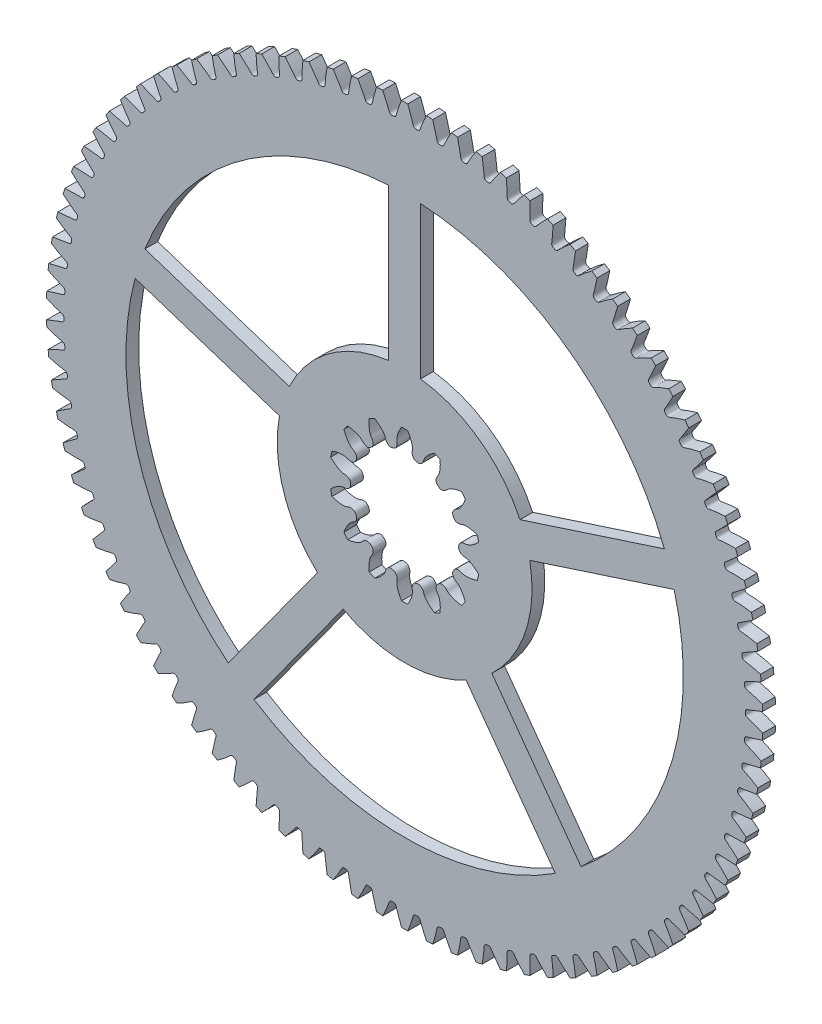
SolidWorks part; units mm, degrees
ref_plane "Alzado" through (0, 0, 0) normal (0, 0, 1) x (1, 0, 0)
ref_plane "Planta" through (0, 0, 0) normal (0, 1, 0) x (1, 0, 0)
ref_plane "Vista lateral" through (0, 0, 0) normal (1, 0, 0) x (0, 0, -1)
ref_axis "Eje1" through (0, 0, 55) along (0, 0, -1)
sketch "SketchRevolveEngranaje Fijo(11.2)" plane through (0, 0, 0) normal (1, 0, 0) x (0, 0, -1)
  line L0 (0, 0) -> (1, 0) construction
  line L1 (-0.1, 0) -> (-0.1, 5.6222)
  line L2 (-0.1, 5.6222) -> (0.1, 5.6222)
  line L3 (0.1, 5.6222) -> (0.1, 0)
  line L4 (0.1, 0) -> (-0.1, 0)
revolve "Engranaje Fijo(11.2)" add sketch "SketchRevolveEngranaje Fijo(11.2)" angle 360 about L0
sketch "SketchToothEngranaje Fijo(11.2)" plane through (0, 0, 0) normal (0, 0, 1) x (1, 0, 0)
  arc A0 (5.6263, 0.1499) -> (5.6263, -0.1499) centre (0, 0) cw
  spline S0 degree 3 poles (5.6263, -0.1499) (5.6166, -0.1454) (5.6021, -0.1388) (5.5829, -0.1304) (5.5688, -0.1243) (5.5549, -0.1184) (5.5413, -0.1127) (5.5278, -0.1072) (5.5146, -0.102) (5.5016, -0.0969) (5.4888, -0.092) (5.4762, -0.0873) (5.4639, -0.0828) (5.4518, -0.0785) (5.4399, -0.0744) (5.4282, -0.0704) (5.4168, -0.0666) (5.4057, -0.063) (5.3936, -0.0592) (5.3845, -0.0566) (5.3783, -0.0544) (5.3759, -0.0535) (5.3735, -0.0525) (5.371, -0.0513) (5.3684, -0.0498) (5.3656, -0.0481) (5.3626, -0.0459) (5.3594, -0.0431) (5.3561, -0.0395) (5.3528, -0.0348) (5.3498, -0.0288) (5.3477, -0.0218) (5.3469, -0.012) (5.3474, 0) (5.3469, 0.012) (5.3477, 0.0218) (5.3498, 0.0288) (5.3528, 0.0348) (5.3561, 0.0395) (5.3594, 0.0431) (5.3626, 0.0459) (5.3656, 0.0481) (5.3684, 0.0498) (5.371, 0.0513) (5.3735, 0.0525) (5.3759, 0.0535) (5.3783, 0.0544) (5.3845, 0.0566) (5.3936, 0.0592) (5.4057, 0.063) (5.4168, 0.0666) (5.4282, 0.0704) (5.4399, 0.0744) (5.4518, 0.0785) (5.4639, 0.0828) (5.4762, 0.0873) (5.4888, 0.092) (5.5016, 0.0969) (5.5146, 0.102) (5.5278, 0.1072) (5.5413, 0.1127) (5.5549, 0.1184) (5.5688, 0.1243) (5.5829, 0.1304) (5.6021, 0.1388) (5.6166, 0.1454) (5.6263, 0.1499) knots 0 0 0 0 0.047965 0.071326 0.094273 0.116806 0.138924 0.160627 0.181917 0.202792 0.223252 0.243298 0.26293 0.282148 0.300951 0.31934 0.337314 0.354874 0.37202 0.393934 0.397608 0.401368 0.40527 0.409387 0.413812 0.418671 0.424124 0.430371 0.437648 0.446186 0.45612 0.467339 0.478619 0.5 0.521381 0.532661 0.54388 0.553814 0.562352 0.569629 0.575876 0.581329 0.586188 0.590613 0.59473 0.598632 0.602392 0.606066 0.62798 0.645126 0.662686 0.68066 0.699049 0.717852 0.73707 0.756702 0.776748 0.797208 0.818083 0.839373 0.861076 0.883194 0.905727 0.928674 0.952035 1 1 1 1
extrude "ToothExtrudeCutEngranaje Fijo(11.2)" cut sketch "SketchToothEngranaje Fijo(11.2)" against normal blind 0.1 and the other way blind 0.1
pattern_circular "PatternEngranaje Fijo(11.2)" count 90 every 4 about axis through (0, 0, 55) along (0, 0, -1) of "ToothExtrudeCutEngranaje Fijo(11.2)"
sketch "AuxiliarySketchEngranaje Fijo(11.2)" plane through (0, 0, 0) normal (0, 0, 1) x (1, 0, 0)
  circle A0 centre (0, 0) radius 5.5 construction
  circle A1 centre (0, 0) radius 5.1683 construction
  circle A2 centre (0, 0) radius 5.383 construction
  circle A3 centre (0, 0) radius 5.6222 construction
  circle A4 centre (0, 0) radius 5.3472 construction
  dimension "PitchDiameter" = 11
  dimension "BaseDiameter" = 10.3366
  dimension "FormDiameter" = 10.7659
  dimension "MajorDiameter" = 11.2444
  dimension "MinorDiameter" = 10.6944
sketch "Croquis5" plane through (0, 0, 0.1) normal (0, 0, 1) x (1, 0, 0)
  line L0 (0, 0) -> (0, 4.375) construction
  line L1 (0, 0) -> (-4.1609, 1.3519) construction
  line L2 (0, 0) -> (4.1609, 1.3519) construction
  line L3 (0, 0) -> (-2.5716, -3.5394) construction
  line L4 (0, 0) -> (2.5716, -3.5394) construction
  line L15 (0.25, 1.9843) -> (0.25, 4.375)
  line L16 (-0.25, 1.9843) -> (-0.25, 4.375)
  line L18 (-1.8099, 0.851) -> (-4.0836, 1.5897)
  line L20 (-1.9644, 0.3754) -> (-4.2381, 1.1142)
  line L22 (1.8099, 0.851) -> (4.0836, 1.5897)
  line L24 (1.9644, 0.3754) -> (4.2381, 1.1142)
  line L26 (1.3686, -1.4584) -> (2.7738, -3.3925)
  line L28 (0.9641, -1.7523) -> (2.3693, -3.6864)
  line L30 (-0.9641, -1.7523) -> (-2.3693, -3.6864)
  line L32 (-1.3686, -1.4584) -> (-2.7738, -3.3925)
  arc A0 (1.3686, -1.4584) -> (1.9644, 0.3754) centre (0, 0) ccw
  arc A1 (-4.2313, 1.112) -> (-2.5716, -3.5394) centre (0, 0) ccw
  arc A3 (-0.25, 1.9843) -> (-1.8099, 0.851) centre (0, 0) ccw
  arc A4 (1.8099, 0.851) -> (0.25, 1.9843) centre (0, 0) ccw
  arc A5 (1.8099, 0.851) -> (0.25, 1.9843) centre (0, 0) ccw
  arc A6 (-0.9641, -1.7523) -> (0.9641, -1.7523) centre (0, 0) ccw
  arc A7 (0, 4.375) -> (-4.0768, 1.5875) centre (0, 0) ccw
  arc A8 (4.1609, 1.3519) -> (0, 4.375) centre (0, 0) ccw
  arc A9 (2.5716, -3.5394) -> (4.1609, 1.3519) centre (0, 0) ccw
  arc A10 (-2.5716, -3.5394) -> (2.5716, -3.5394) centre (0, 0) ccw
  arc A11 (-1.9644, 0.3754) -> (-1.3686, -1.4584) centre (0, 0) ccw
  arc A12 (-0.9641, -1.7523) -> (0.9641, -1.7523) centre (0, 0) ccw
  arc A13 (1.1619, 0.2163) -> (1.1406, 0.3093) centre (0, 0) ccw
  arc A14 (0.953, 0.699) -> (0.8935, 0.7735) centre (0, 0) ccw
  arc A15 (0.5553, 1.0432) -> (0.4694, 1.0846) centre (0, 0) ccw
  arc A16 (0.0477, 1.1809) -> (-0.0477, 1.1809) centre (0, 0) ccw
  arc A17 (-0.4694, 1.0846) -> (-0.5553, 1.0432) centre (0, 0) ccw
  arc A18 (-0.8935, 0.7735) -> (-0.953, 0.699) centre (0, 0) ccw
  arc A19 (-1.1406, 0.3093) -> (-1.1619, 0.2163) centre (0, 0) ccw
  arc A20 (-1.1619, -0.2163) -> (-1.1406, -0.3093) centre (0, 0) ccw
  arc A21 (-0.953, -0.699) -> (-0.8935, -0.7735) centre (0, 0) ccw
  arc A22 (-0.5553, -1.0432) -> (-0.4694, -1.0846) centre (0, 0) ccw
  arc A23 (-0.0477, -1.1809) -> (0.0477, -1.1809) centre (0, 0) ccw
  arc A24 (0.4694, -1.0846) -> (0.5553, -1.0432) centre (0, 0) ccw
  arc A25 (0.8935, -0.7735) -> (0.953, -0.699) centre (0, 0) ccw
  arc A26 (1.1406, -0.3093) -> (1.1619, -0.2163) centre (0, 0) ccw
  spline S0 degree 3 poles (1.1619, 0.2163) (1.1532, 0.2075) (1.1392, 0.1941) (1.1195, 0.1771) (1.104, 0.1645) (1.089, 0.1533) (1.0747, 0.1432) (1.061, 0.1344) (1.048, 0.1266) (1.0358, 0.1199) (1.0245, 0.1142) (1.014, 0.1093) (1.0046, 0.1054) (0.9961, 0.1021) (0.9887, 0.0996) (0.9823, 0.0977) (0.9738, 0.0954) (0.9644, 0.0944) (0.9543, 0.0941) (0.9465, 0.0934) (0.9389, 0.0924) (0.9315, 0.0913) (0.9244, 0.0898) (0.9175, 0.0881) (0.9108, 0.0861) (0.9043, 0.0838) (0.8981, 0.0813) (0.892, 0.0784) (0.8862, 0.0751) (0.8806, 0.0714) (0.8752, 0.0673) (0.87, 0.0627) (0.8651, 0.0575) (0.8606, 0.0516) (0.8566, 0.0449) (0.8533, 0.0376) (0.8508, 0.0295) (0.8496, 0.0218) (0.8491, 0.0119) (0.8497, 0) (0.8491, -0.0119) (0.8496, -0.0218) (0.8508, -0.0295) (0.8533, -0.0376) (0.8566, -0.0449) (0.8606, -0.0516) (0.8651, -0.0575) (0.87, -0.0627) (0.8752, -0.0673) (0.8806, -0.0714) (0.8862, -0.0751) (0.892, -0.0784) (0.8981, -0.0813) (0.9043, -0.0838) (0.9108, -0.0861) (0.9175, -0.0881) (0.9244, -0.0898) (0.9315, -0.0913) (0.9389, -0.0924) (0.9465, -0.0934) (0.9543, -0.0941) (0.9644, -0.0944) (0.9738, -0.0954) (0.9823, -0.0977) (0.9887, -0.0996) (0.9961, -0.1021) (1.0046, -0.1054) (1.014, -0.1093) (1.0245, -0.1142) (1.0358, -0.1199) (1.048, -0.1266) (1.061, -0.1344) (1.0747, -0.1432) (1.089, -0.1533) (1.104, -0.1645) (1.1195, -0.1771) (1.1392, -0.1941) (1.1532, -0.2075) (1.1619, -0.2163) knots 0.010866 0.010866 0.010866 0.010866 0.0554 0.080914 0.104969 0.127567 0.148706 0.168388 0.186612 0.203378 0.218686 0.232536 0.244928 0.255863 0.265339 0.273357 0.279918 0.297272 0.307044 0.316542 0.325781 0.334777 0.343546 0.352112 0.360499 0.368737 0.376863 0.384917 0.39295 0.401018 0.409187 0.41753 0.426123 0.43504 0.444343 0.454063 0.464189 0.474651 0.482386 0.5 0.517614 0.525349 0.535811 0.545937 0.555657 0.56496 0.573877 0.58247 0.590813 0.598982 0.60705 0.615083 0.623137 0.631263 0.639501 0.647888 0.656454 0.665223 0.674219 0.683458 0.692956 0.702728 0.720082 0.726643 0.734661 0.744137 0.755072 0.767464 0.781314 0.796622 0.813388 0.831612 0.851294 0.872433 0.895031 0.919086 0.9446 0.989134 0.989134 0.989134 0.989134
  spline S1 degree 3 poles (1.1406, -0.3093) (1.129, -0.3134) (1.1106, -0.3194) (1.0855, -0.3262) (1.0661, -0.3308) (1.0477, -0.3344) (1.0304, -0.3372) (1.0142, -0.3393) (0.9991, -0.3406) (0.9852, -0.3414) (0.9726, -0.3416) (0.9611, -0.3415) (0.9508, -0.3409) (0.9418, -0.3402) (0.934, -0.3392) (0.9274, -0.3382) (0.9187, -0.3366) (0.9099, -0.3334) (0.9006, -0.3293) (0.8933, -0.3265) (0.886, -0.3241) (0.8788, -0.3219) (0.8718, -0.3202) (0.8648, -0.3187) (0.8579, -0.3176) (0.8511, -0.3168) (0.8444, -0.3165) (0.8377, -0.3164) (0.831, -0.3169) (0.8244, -0.3177) (0.8177, -0.3191) (0.811, -0.321) (0.8044, -0.3236) (0.7977, -0.327) (0.7913, -0.3312) (0.7851, -0.3364) (0.7794, -0.3425) (0.7749, -0.349) (0.7702, -0.3577) (0.7655, -0.3687) (0.7599, -0.3791) (0.756, -0.3882) (0.7537, -0.3958) (0.7525, -0.4041) (0.7523, -0.4121) (0.753, -0.4198) (0.7545, -0.4271) (0.7566, -0.434) (0.7593, -0.4404) (0.7624, -0.4464) (0.7659, -0.4522) (0.7697, -0.4576) (0.7739, -0.4629) (0.7784, -0.4679) (0.7832, -0.4727) (0.7884, -0.4774) (0.7939, -0.482) (0.7997, -0.4864) (0.8058, -0.4906) (0.8122, -0.4948) (0.819, -0.4988) (0.828, -0.5035) (0.836, -0.5084) (0.8426, -0.5142) (0.8475, -0.5187) (0.8531, -0.5242) (0.8594, -0.5308) (0.8662, -0.5385) (0.8735, -0.5474) (0.8812, -0.5574) (0.8893, -0.5688) (0.8976, -0.5814) (0.9061, -0.5953) (0.9147, -0.6106) (0.9233, -0.6273) (0.9318, -0.6453) (0.9421, -0.6692) (0.949, -0.6873) (0.953, -0.699) knots 0.010866 0.010866 0.010866 0.010866 0.0554 0.080914 0.104969 0.127567 0.148706 0.168388 0.186612 0.203378 0.218686 0.232536 0.244928 0.255863 0.265339 0.273357 0.279918 0.297272 0.307044 0.316542 0.325781 0.334777 0.343546 0.352112 0.360499 0.368737 0.376863 0.384917 0.39295 0.401018 0.409187 0.41753 0.426123 0.43504 0.444343 0.454063 0.464189 0.474651 0.482386 0.5 0.517614 0.525349 0.535811 0.545937 0.555657 0.56496 0.573877 0.58247 0.590813 0.598982 0.60705 0.615083 0.623137 0.631263 0.639501 0.647888 0.656454 0.665223 0.674219 0.683458 0.692956 0.702728 0.720082 0.726643 0.734661 0.744137 0.755072 0.767464 0.781314 0.796622 0.813388 0.831612 0.851294 0.872433 0.895031 0.919086 0.9446 0.989134 0.989134 0.989134 0.989134
  spline S2 degree 3 poles (0.8935, -0.7735) (0.8812, -0.7722) (0.8621, -0.7696) (0.8365, -0.7649) (0.817, -0.7606) (0.7988, -0.7559) (0.782, -0.7509) (0.7666, -0.7457) (0.7524, -0.7404) (0.7396, -0.7351) (0.728, -0.7298) (0.7177, -0.7246) (0.7087, -0.7197) (0.7009, -0.7151) (0.6943, -0.7109) (0.6888, -0.7071) (0.6817, -0.7019) (0.6751, -0.6952) (0.6686, -0.6875) (0.6631, -0.6818) (0.6576, -0.6764) (0.6521, -0.6714) (0.6465, -0.6667) (0.6409, -0.6624) (0.6352, -0.6584) (0.6294, -0.6548) (0.6235, -0.6515) (0.6174, -0.6486) (0.6113, -0.646) (0.6049, -0.6439) (0.5983, -0.6423) (0.5914, -0.6411) (0.5843, -0.6405) (0.5769, -0.6407) (0.5692, -0.6417) (0.5614, -0.6437) (0.5536, -0.6468) (0.5467, -0.6507) (0.5387, -0.6565) (0.5298, -0.6643) (0.5201, -0.6713) (0.5127, -0.6778) (0.5074, -0.6836) (0.5026, -0.6905) (0.4989, -0.6977) (0.4963, -0.705) (0.4945, -0.7122) (0.4934, -0.7193) (0.493, -0.7262) (0.4932, -0.733) (0.4938, -0.7397) (0.4949, -0.7463) (0.4964, -0.7528) (0.4983, -0.7593) (0.5005, -0.7658) (0.5032, -0.7722) (0.5061, -0.7787) (0.5094, -0.7852) (0.5131, -0.7917) (0.5171, -0.7982) (0.5215, -0.8048) (0.5275, -0.8129) (0.5326, -0.8208) (0.5361, -0.8289) (0.5385, -0.8351) (0.5412, -0.8425) (0.544, -0.8511) (0.5468, -0.861) (0.5495, -0.8721) (0.5521, -0.8846) (0.5544, -0.8983) (0.5564, -0.9133) (0.558, -0.9295) (0.5592, -0.947) (0.5597, -0.9657) (0.5596, -0.9857) (0.5585, -1.0117) (0.5568, -1.031) (0.5553, -1.0432) knots 0.010866 0.010866 0.010866 0.010866 0.0554 0.080914 0.104969 0.127567 0.148706 0.168388 0.186612 0.203378 0.218686 0.232536 0.244928 0.255863 0.265339 0.273357 0.279918 0.297272 0.307044 0.316542 0.325781 0.334777 0.343546 0.352112 0.360499 0.368737 0.376863 0.384917 0.39295 0.401018 0.409187 0.41753 0.426123 0.43504 0.444343 0.454063 0.464189 0.474651 0.482386 0.5 0.517614 0.525349 0.535811 0.545937 0.555657 0.56496 0.573877 0.58247 0.590813 0.598982 0.60705 0.615083 0.623137 0.631263 0.639501 0.647888 0.656454 0.665223 0.674219 0.683458 0.692956 0.702728 0.720082 0.726643 0.734661 0.744137 0.755072 0.767464 0.781314 0.796622 0.813388 0.831612 0.851294 0.872433 0.895031 0.919086 0.9446 0.989134 0.989134 0.989134 0.989134
  spline S3 degree 3 poles (0.4694, -1.0846) (0.4589, -1.0781) (0.4428, -1.0674) (0.4218, -1.0521) (0.4061, -1.0397) (0.3918, -1.0276) (0.3788, -1.0158) (0.3671, -1.0045) (0.3566, -0.9935) (0.3474, -0.9831) (0.3393, -0.9734) (0.3323, -0.9643) (0.3263, -0.9559) (0.3212, -0.9484) (0.3171, -0.9417) (0.3138, -0.9359) (0.3097, -0.9281) (0.3066, -0.9193) (0.3041, -0.9095) (0.3016, -0.902) (0.299, -0.8948) (0.2962, -0.8878) (0.2932, -0.8812) (0.29, -0.8749) (0.2866, -0.8688) (0.283, -0.863) (0.2791, -0.8575) (0.2749, -0.8522) (0.2704, -0.8473) (0.2656, -0.8426) (0.2604, -0.8382) (0.2547, -0.8342) (0.2485, -0.8306) (0.2418, -0.8275) (0.2344, -0.8251) (0.2265, -0.8235) (0.2181, -0.8229) (0.2103, -0.8235) (0.2005, -0.8252) (0.1891, -0.8284) (0.1774, -0.8305) (0.1678, -0.8331) (0.1605, -0.836) (0.1532, -0.8402) (0.1468, -0.8451) (0.1412, -0.8505) (0.1365, -0.8562) (0.1325, -0.8621) (0.1291, -0.8682) (0.1263, -0.8744) (0.124, -0.8807) (0.1221, -0.8871) (0.1206, -0.8936) (0.1195, -0.9003) (0.1187, -0.9071) (0.1183, -0.9141) (0.1181, -0.9212) (0.1183, -0.9284) (0.1188, -0.9359) (0.1196, -0.9435) (0.1206, -0.9513) (0.1226, -0.9613) (0.1237, -0.9706) (0.1233, -0.9794) (0.1229, -0.986) (0.1221, -0.9938) (0.1208, -1.0028) (0.119, -1.013) (0.1167, -1.0242) (0.1136, -1.0365) (0.1098, -1.0499) (0.1051, -1.0643) (0.0995, -1.0796) (0.0929, -1.0958) (0.0853, -1.113) (0.0765, -1.1309) (0.0642, -1.1538) (0.0543, -1.1705) (0.0477, -1.1809) knots 0.010866 0.010866 0.010866 0.010866 0.0554 0.080914 0.104969 0.127567 0.148706 0.168388 0.186612 0.203378 0.218686 0.232536 0.244928 0.255863 0.265339 0.273357 0.279918 0.297272 0.307044 0.316542 0.325781 0.334777 0.343546 0.352112 0.360499 0.368737 0.376863 0.384917 0.39295 0.401018 0.409187 0.41753 0.426123 0.43504 0.444343 0.454063 0.464189 0.474651 0.482386 0.5 0.517614 0.525349 0.535811 0.545937 0.555657 0.56496 0.573877 0.58247 0.590813 0.598982 0.60705 0.615083 0.623137 0.631263 0.639501 0.647888 0.656454 0.665223 0.674219 0.683458 0.692956 0.702728 0.720082 0.726643 0.734661 0.744137 0.755072 0.767464 0.781314 0.796622 0.813388 0.831612 0.851294 0.872433 0.895031 0.919086 0.9446 0.989134 0.989134 0.989134 0.989134
  spline S4 degree 3 poles (-0.0477, -1.1809) (-0.0543, -1.1705) (-0.0642, -1.1538) (-0.0765, -1.1309) (-0.0853, -1.113) (-0.0929, -1.0958) (-0.0995, -1.0796) (-0.1051, -1.0643) (-0.1098, -1.0499) (-0.1136, -1.0365) (-0.1167, -1.0242) (-0.119, -1.013) (-0.1208, -1.0028) (-0.1221, -0.9938) (-0.1229, -0.986) (-0.1233, -0.9794) (-0.1237, -0.9706) (-0.1226, -0.9613) (-0.1206, -0.9513) (-0.1196, -0.9435) (-0.1188, -0.9359) (-0.1183, -0.9284) (-0.1181, -0.9212) (-0.1183, -0.9141) (-0.1187, -0.9071) (-0.1195, -0.9003) (-0.1206, -0.8936) (-0.1221, -0.8871) (-0.124, -0.8807) (-0.1263, -0.8744) (-0.1291, -0.8682) (-0.1325, -0.8621) (-0.1365, -0.8562) (-0.1412, -0.8505) (-0.1468, -0.8451) (-0.1532, -0.8402) (-0.1605, -0.836) (-0.1678, -0.8331) (-0.1774, -0.8305) (-0.1891, -0.8284) (-0.2005, -0.8252) (-0.2103, -0.8235) (-0.2181, -0.8229) (-0.2265, -0.8235) (-0.2344, -0.8251) (-0.2418, -0.8275) (-0.2485, -0.8306) (-0.2547, -0.8342) (-0.2604, -0.8382) (-0.2656, -0.8426) (-0.2704, -0.8473) (-0.2749, -0.8522) (-0.2791, -0.8575) (-0.283, -0.863) (-0.2866, -0.8688) (-0.29, -0.8749) (-0.2932, -0.8812) (-0.2962, -0.8878) (-0.299, -0.8948) (-0.3016, -0.902) (-0.3041, -0.9095) (-0.3066, -0.9193) (-0.3097, -0.9281) (-0.3138, -0.9359) (-0.3171, -0.9417) (-0.3212, -0.9484) (-0.3263, -0.9559) (-0.3323, -0.9643) (-0.3393, -0.9734) (-0.3474, -0.9831) (-0.3566, -0.9935) (-0.3671, -1.0045) (-0.3788, -1.0158) (-0.3918, -1.0276) (-0.4061, -1.0397) (-0.4218, -1.0521) (-0.4428, -1.0674) (-0.4589, -1.0781) (-0.4694, -1.0846) knots 0.010866 0.010866 0.010866 0.010866 0.0554 0.080914 0.104969 0.127567 0.148706 0.168388 0.186612 0.203378 0.218686 0.232536 0.244928 0.255863 0.265339 0.273357 0.279918 0.297272 0.307044 0.316542 0.325781 0.334777 0.343546 0.352112 0.360499 0.368737 0.376863 0.384917 0.39295 0.401018 0.409187 0.41753 0.426123 0.43504 0.444343 0.454063 0.464189 0.474651 0.482386 0.5 0.517614 0.525349 0.535811 0.545937 0.555657 0.56496 0.573877 0.58247 0.590813 0.598982 0.60705 0.615083 0.623137 0.631263 0.639501 0.647888 0.656454 0.665223 0.674219 0.683458 0.692956 0.702728 0.720082 0.726643 0.734661 0.744137 0.755072 0.767464 0.781314 0.796622 0.813388 0.831612 0.851294 0.872433 0.895031 0.919086 0.9446 0.989134 0.989134 0.989134 0.989134
  spline S5 degree 3 poles (-0.5553, -1.0432) (-0.5568, -1.031) (-0.5585, -1.0117) (-0.5596, -0.9857) (-0.5597, -0.9657) (-0.5592, -0.947) (-0.558, -0.9295) (-0.5564, -0.9133) (-0.5544, -0.8983) (-0.5521, -0.8846) (-0.5495, -0.8721) (-0.5468, -0.861) (-0.544, -0.8511) (-0.5412, -0.8425) (-0.5385, -0.8351) (-0.5361, -0.8289) (-0.5326, -0.8208) (-0.5275, -0.8129) (-0.5215, -0.8048) (-0.5171, -0.7982) (-0.5131, -0.7917) (-0.5094, -0.7852) (-0.5061, -0.7787) (-0.5032, -0.7722) (-0.5005, -0.7658) (-0.4983, -0.7593) (-0.4964, -0.7528) (-0.4949, -0.7463) (-0.4938, -0.7397) (-0.4932, -0.733) (-0.493, -0.7262) (-0.4934, -0.7193) (-0.4945, -0.7122) (-0.4963, -0.705) (-0.4989, -0.6977) (-0.5026, -0.6905) (-0.5074, -0.6836) (-0.5127, -0.6778) (-0.5201, -0.6713) (-0.5298, -0.6643) (-0.5387, -0.6565) (-0.5467, -0.6507) (-0.5536, -0.6468) (-0.5614, -0.6437) (-0.5692, -0.6417) (-0.5769, -0.6407) (-0.5843, -0.6405) (-0.5914, -0.6411) (-0.5983, -0.6423) (-0.6049, -0.6439) (-0.6113, -0.646) (-0.6174, -0.6486) (-0.6235, -0.6515) (-0.6294, -0.6548) (-0.6352, -0.6584) (-0.6409, -0.6624) (-0.6465, -0.6667) (-0.6521, -0.6714) (-0.6576, -0.6764) (-0.6631, -0.6818) (-0.6686, -0.6875) (-0.6751, -0.6952) (-0.6817, -0.7019) (-0.6888, -0.7071) (-0.6943, -0.7109) (-0.7009, -0.7151) (-0.7087, -0.7197) (-0.7177, -0.7246) (-0.728, -0.7298) (-0.7396, -0.7351) (-0.7524, -0.7404) (-0.7666, -0.7457) (-0.782, -0.7509) (-0.7988, -0.7559) (-0.817, -0.7606) (-0.8365, -0.7649) (-0.8621, -0.7696) (-0.8812, -0.7722) (-0.8935, -0.7735) knots 0.010866 0.010866 0.010866 0.010866 0.0554 0.080914 0.104969 0.127567 0.148706 0.168388 0.186612 0.203378 0.218686 0.232536 0.244928 0.255863 0.265339 0.273357 0.279918 0.297272 0.307044 0.316542 0.325781 0.334777 0.343546 0.352112 0.360499 0.368737 0.376863 0.384917 0.39295 0.401018 0.409187 0.41753 0.426123 0.43504 0.444343 0.454063 0.464189 0.474651 0.482386 0.5 0.517614 0.525349 0.535811 0.545937 0.555657 0.56496 0.573877 0.58247 0.590813 0.598982 0.60705 0.615083 0.623137 0.631263 0.639501 0.647888 0.656454 0.665223 0.674219 0.683458 0.692956 0.702728 0.720082 0.726643 0.734661 0.744137 0.755072 0.767464 0.781314 0.796622 0.813388 0.831612 0.851294 0.872433 0.895031 0.919086 0.9446 0.989134 0.989134 0.989134 0.989134
  spline S6 degree 3 poles (-0.953, -0.699) (-0.949, -0.6873) (-0.9421, -0.6692) (-0.9318, -0.6453) (-0.9233, -0.6273) (-0.9147, -0.6106) (-0.9061, -0.5953) (-0.8976, -0.5814) (-0.8893, -0.5688) (-0.8812, -0.5574) (-0.8735, -0.5474) (-0.8662, -0.5385) (-0.8594, -0.5308) (-0.8531, -0.5242) (-0.8475, -0.5187) (-0.8426, -0.5142) (-0.836, -0.5084) (-0.828, -0.5035) (-0.819, -0.4988) (-0.8122, -0.4948) (-0.8058, -0.4906) (-0.7997, -0.4864) (-0.7939, -0.482) (-0.7884, -0.4774) (-0.7832, -0.4727) (-0.7784, -0.4679) (-0.7739, -0.4629) (-0.7697, -0.4576) (-0.7659, -0.4522) (-0.7624, -0.4464) (-0.7593, -0.4404) (-0.7566, -0.434) (-0.7545, -0.4271) (-0.753, -0.4198) (-0.7523, -0.4121) (-0.7525, -0.4041) (-0.7537, -0.3958) (-0.756, -0.3882) (-0.7599, -0.3791) (-0.7655, -0.3687) (-0.7702, -0.3577) (-0.7749, -0.349) (-0.7794, -0.3425) (-0.7851, -0.3364) (-0.7913, -0.3312) (-0.7977, -0.327) (-0.8044, -0.3236) (-0.811, -0.321) (-0.8177, -0.3191) (-0.8244, -0.3177) (-0.831, -0.3169) (-0.8377, -0.3164) (-0.8444, -0.3165) (-0.8511, -0.3168) (-0.8579, -0.3176) (-0.8648, -0.3187) (-0.8718, -0.3202) (-0.8788, -0.3219) (-0.886, -0.3241) (-0.8933, -0.3265) (-0.9006, -0.3293) (-0.9099, -0.3334) (-0.9187, -0.3366) (-0.9274, -0.3382) (-0.934, -0.3392) (-0.9418, -0.3402) (-0.9508, -0.3409) (-0.9611, -0.3415) (-0.9726, -0.3416) (-0.9852, -0.3414) (-0.9991, -0.3406) (-1.0142, -0.3393) (-1.0304, -0.3372) (-1.0477, -0.3344) (-1.0661, -0.3308) (-1.0855, -0.3262) (-1.1106, -0.3194) (-1.129, -0.3134) (-1.1406, -0.3093) knots 0.010866 0.010866 0.010866 0.010866 0.0554 0.080914 0.104969 0.127567 0.148706 0.168388 0.186612 0.203378 0.218686 0.232536 0.244928 0.255863 0.265339 0.273357 0.279918 0.297272 0.307044 0.316542 0.325781 0.334777 0.343546 0.352112 0.360499 0.368737 0.376863 0.384917 0.39295 0.401018 0.409187 0.41753 0.426123 0.43504 0.444343 0.454063 0.464189 0.474651 0.482386 0.5 0.517614 0.525349 0.535811 0.545937 0.555657 0.56496 0.573877 0.58247 0.590813 0.598982 0.60705 0.615083 0.623137 0.631263 0.639501 0.647888 0.656454 0.665223 0.674219 0.683458 0.692956 0.702728 0.720082 0.726643 0.734661 0.744137 0.755072 0.767464 0.781314 0.796622 0.813388 0.831612 0.851294 0.872433 0.895031 0.919086 0.9446 0.989134 0.989134 0.989134 0.989134
  spline S7 degree 3 poles (-1.1619, -0.2163) (-1.1532, -0.2075) (-1.1392, -0.1941) (-1.1195, -0.1771) (-1.104, -0.1645) (-1.089, -0.1533) (-1.0747, -0.1432) (-1.061, -0.1344) (-1.048, -0.1266) (-1.0358, -0.1199) (-1.0245, -0.1142) (-1.014, -0.1093) (-1.0046, -0.1054) (-0.9961, -0.1021) (-0.9887, -0.0996) (-0.9823, -0.0977) (-0.9738, -0.0954) (-0.9644, -0.0944) (-0.9543, -0.0941) (-0.9465, -0.0934) (-0.9389, -0.0924) (-0.9315, -0.0913) (-0.9244, -0.0898) (-0.9175, -0.0881) (-0.9108, -0.0861) (-0.9043, -0.0838) (-0.8981, -0.0813) (-0.892, -0.0784) (-0.8862, -0.0751) (-0.8806, -0.0714) (-0.8752, -0.0673) (-0.87, -0.0627) (-0.8651, -0.0575) (-0.8606, -0.0516) (-0.8566, -0.0449) (-0.8533, -0.0376) (-0.8508, -0.0295) (-0.8496, -0.0218) (-0.8491, -0.0119) (-0.8497, 0) (-0.8491, 0.0119) (-0.8496, 0.0218) (-0.8508, 0.0295) (-0.8533, 0.0376) (-0.8566, 0.0449) (-0.8606, 0.0516) (-0.8651, 0.0575) (-0.87, 0.0627) (-0.8752, 0.0673) (-0.8806, 0.0714) (-0.8862, 0.0751) (-0.892, 0.0784) (-0.8981, 0.0813) (-0.9043, 0.0838) (-0.9108, 0.0861) (-0.9175, 0.0881) (-0.9244, 0.0898) (-0.9315, 0.0913) (-0.9389, 0.0924) (-0.9465, 0.0934) (-0.9543, 0.0941) (-0.9644, 0.0944) (-0.9738, 0.0954) (-0.9823, 0.0977) (-0.9887, 0.0996) (-0.9961, 0.1021) (-1.0046, 0.1054) (-1.014, 0.1093) (-1.0245, 0.1142) (-1.0358, 0.1199) (-1.048, 0.1266) (-1.061, 0.1344) (-1.0747, 0.1432) (-1.089, 0.1533) (-1.104, 0.1645) (-1.1195, 0.1771) (-1.1392, 0.1941) (-1.1532, 0.2075) (-1.1619, 0.2163) knots 0.010866 0.010866 0.010866 0.010866 0.0554 0.080914 0.104969 0.127567 0.148706 0.168388 0.186612 0.203378 0.218686 0.232536 0.244928 0.255863 0.265339 0.273357 0.279918 0.297272 0.307044 0.316542 0.325781 0.334777 0.343546 0.352112 0.360499 0.368737 0.376863 0.384917 0.39295 0.401018 0.409187 0.41753 0.426123 0.43504 0.444343 0.454063 0.464189 0.474651 0.482386 0.5 0.517614 0.525349 0.535811 0.545937 0.555657 0.56496 0.573877 0.58247 0.590813 0.598982 0.60705 0.615083 0.623137 0.631263 0.639501 0.647888 0.656454 0.665223 0.674219 0.683458 0.692956 0.702728 0.720082 0.726643 0.734661 0.744137 0.755072 0.767464 0.781314 0.796622 0.813388 0.831612 0.851294 0.872433 0.895031 0.919086 0.9446 0.989134 0.989134 0.989134 0.989134
  spline S8 degree 3 poles (-1.1406, 0.3093) (-1.129, 0.3134) (-1.1106, 0.3194) (-1.0855, 0.3262) (-1.0661, 0.3308) (-1.0477, 0.3344) (-1.0304, 0.3372) (-1.0142, 0.3393) (-0.9991, 0.3406) (-0.9852, 0.3414) (-0.9726, 0.3416) (-0.9611, 0.3415) (-0.9508, 0.3409) (-0.9418, 0.3402) (-0.934, 0.3392) (-0.9274, 0.3382) (-0.9187, 0.3366) (-0.9099, 0.3334) (-0.9006, 0.3293) (-0.8933, 0.3265) (-0.886, 0.3241) (-0.8788, 0.3219) (-0.8718, 0.3202) (-0.8648, 0.3187) (-0.8579, 0.3176) (-0.8511, 0.3168) (-0.8444, 0.3165) (-0.8377, 0.3164) (-0.831, 0.3169) (-0.8244, 0.3177) (-0.8177, 0.3191) (-0.811, 0.321) (-0.8044, 0.3236) (-0.7977, 0.327) (-0.7913, 0.3312) (-0.7851, 0.3364) (-0.7794, 0.3425) (-0.7749, 0.349) (-0.7702, 0.3577) (-0.7655, 0.3687) (-0.7599, 0.3791) (-0.756, 0.3882) (-0.7537, 0.3958) (-0.7525, 0.4041) (-0.7523, 0.4121) (-0.753, 0.4198) (-0.7545, 0.4271) (-0.7566, 0.434) (-0.7593, 0.4404) (-0.7624, 0.4464) (-0.7659, 0.4522) (-0.7697, 0.4576) (-0.7739, 0.4629) (-0.7784, 0.4679) (-0.7832, 0.4727) (-0.7884, 0.4774) (-0.7939, 0.482) (-0.7997, 0.4864) (-0.8058, 0.4906) (-0.8122, 0.4948) (-0.819, 0.4988) (-0.828, 0.5035) (-0.836, 0.5084) (-0.8426, 0.5142) (-0.8475, 0.5187) (-0.8531, 0.5242) (-0.8594, 0.5308) (-0.8662, 0.5385) (-0.8735, 0.5474) (-0.8812, 0.5574) (-0.8893, 0.5688) (-0.8976, 0.5814) (-0.9061, 0.5953) (-0.9147, 0.6106) (-0.9233, 0.6273) (-0.9318, 0.6453) (-0.9421, 0.6692) (-0.949, 0.6873) (-0.953, 0.699) knots 0.010866 0.010866 0.010866 0.010866 0.0554 0.080914 0.104969 0.127567 0.148706 0.168388 0.186612 0.203378 0.218686 0.232536 0.244928 0.255863 0.265339 0.273357 0.279918 0.297272 0.307044 0.316542 0.325781 0.334777 0.343546 0.352112 0.360499 0.368737 0.376863 0.384917 0.39295 0.401018 0.409187 0.41753 0.426123 0.43504 0.444343 0.454063 0.464189 0.474651 0.482386 0.5 0.517614 0.525349 0.535811 0.545937 0.555657 0.56496 0.573877 0.58247 0.590813 0.598982 0.60705 0.615083 0.623137 0.631263 0.639501 0.647888 0.656454 0.665223 0.674219 0.683458 0.692956 0.702728 0.720082 0.726643 0.734661 0.744137 0.755072 0.767464 0.781314 0.796622 0.813388 0.831612 0.851294 0.872433 0.895031 0.919086 0.9446 0.989134 0.989134 0.989134 0.989134
  spline S9 degree 3 poles (-0.8935, 0.7735) (-0.8812, 0.7722) (-0.8621, 0.7696) (-0.8365, 0.7649) (-0.817, 0.7606) (-0.7988, 0.7559) (-0.782, 0.7509) (-0.7666, 0.7457) (-0.7524, 0.7404) (-0.7396, 0.7351) (-0.728, 0.7298) (-0.7177, 0.7246) (-0.7087, 0.7197) (-0.7009, 0.7151) (-0.6943, 0.7109) (-0.6888, 0.7071) (-0.6817, 0.7019) (-0.6751, 0.6952) (-0.6686, 0.6875) (-0.6631, 0.6818) (-0.6576, 0.6764) (-0.6521, 0.6714) (-0.6465, 0.6667) (-0.6409, 0.6624) (-0.6352, 0.6584) (-0.6294, 0.6548) (-0.6235, 0.6515) (-0.6174, 0.6486) (-0.6113, 0.646) (-0.6049, 0.6439) (-0.5983, 0.6423) (-0.5914, 0.6411) (-0.5843, 0.6405) (-0.5769, 0.6407) (-0.5692, 0.6417) (-0.5614, 0.6437) (-0.5536, 0.6468) (-0.5467, 0.6507) (-0.5387, 0.6565) (-0.5298, 0.6643) (-0.5201, 0.6713) (-0.5127, 0.6778) (-0.5074, 0.6836) (-0.5026, 0.6905) (-0.4989, 0.6977) (-0.4963, 0.705) (-0.4945, 0.7122) (-0.4934, 0.7193) (-0.493, 0.7262) (-0.4932, 0.733) (-0.4938, 0.7397) (-0.4949, 0.7463) (-0.4964, 0.7528) (-0.4983, 0.7593) (-0.5005, 0.7658) (-0.5032, 0.7722) (-0.5061, 0.7787) (-0.5094, 0.7852) (-0.5131, 0.7917) (-0.5171, 0.7982) (-0.5215, 0.8048) (-0.5275, 0.8129) (-0.5326, 0.8208) (-0.5361, 0.8289) (-0.5385, 0.8351) (-0.5412, 0.8425) (-0.544, 0.8511) (-0.5468, 0.861) (-0.5495, 0.8721) (-0.5521, 0.8846) (-0.5544, 0.8983) (-0.5564, 0.9133) (-0.558, 0.9295) (-0.5592, 0.947) (-0.5597, 0.9657) (-0.5596, 0.9857) (-0.5585, 1.0117) (-0.5568, 1.031) (-0.5553, 1.0432) knots 0.010866 0.010866 0.010866 0.010866 0.0554 0.080914 0.104969 0.127567 0.148706 0.168388 0.186612 0.203378 0.218686 0.232536 0.244928 0.255863 0.265339 0.273357 0.279918 0.297272 0.307044 0.316542 0.325781 0.334777 0.343546 0.352112 0.360499 0.368737 0.376863 0.384917 0.39295 0.401018 0.409187 0.41753 0.426123 0.43504 0.444343 0.454063 0.464189 0.474651 0.482386 0.5 0.517614 0.525349 0.535811 0.545937 0.555657 0.56496 0.573877 0.58247 0.590813 0.598982 0.60705 0.615083 0.623137 0.631263 0.639501 0.647888 0.656454 0.665223 0.674219 0.683458 0.692956 0.702728 0.720082 0.726643 0.734661 0.744137 0.755072 0.767464 0.781314 0.796622 0.813388 0.831612 0.851294 0.872433 0.895031 0.919086 0.9446 0.989134 0.989134 0.989134 0.989134
  spline S10 degree 3 poles (-0.4694, 1.0846) (-0.4589, 1.0781) (-0.4428, 1.0674) (-0.4218, 1.0521) (-0.4061, 1.0397) (-0.3918, 1.0276) (-0.3788, 1.0158) (-0.3671, 1.0045) (-0.3566, 0.9935) (-0.3474, 0.9831) (-0.3393, 0.9734) (-0.3323, 0.9643) (-0.3263, 0.9559) (-0.3212, 0.9484) (-0.3171, 0.9417) (-0.3138, 0.9359) (-0.3097, 0.9281) (-0.3066, 0.9193) (-0.3041, 0.9095) (-0.3016, 0.902) (-0.299, 0.8948) (-0.2962, 0.8878) (-0.2932, 0.8812) (-0.29, 0.8749) (-0.2866, 0.8688) (-0.283, 0.863) (-0.2791, 0.8575) (-0.2749, 0.8522) (-0.2704, 0.8473) (-0.2656, 0.8426) (-0.2604, 0.8382) (-0.2547, 0.8342) (-0.2485, 0.8306) (-0.2418, 0.8275) (-0.2344, 0.8251) (-0.2265, 0.8235) (-0.2181, 0.8229) (-0.2103, 0.8235) (-0.2005, 0.8252) (-0.1891, 0.8284) (-0.1774, 0.8305) (-0.1678, 0.8331) (-0.1605, 0.836) (-0.1532, 0.8402) (-0.1468, 0.8451) (-0.1412, 0.8505) (-0.1365, 0.8562) (-0.1325, 0.8621) (-0.1291, 0.8682) (-0.1263, 0.8744) (-0.124, 0.8807) (-0.1221, 0.8871) (-0.1206, 0.8936) (-0.1195, 0.9003) (-0.1187, 0.9071) (-0.1183, 0.9141) (-0.1181, 0.9212) (-0.1183, 0.9284) (-0.1188, 0.9359) (-0.1196, 0.9435) (-0.1206, 0.9513) (-0.1226, 0.9613) (-0.1237, 0.9706) (-0.1233, 0.9794) (-0.1229, 0.986) (-0.1221, 0.9938) (-0.1208, 1.0028) (-0.119, 1.013) (-0.1167, 1.0242) (-0.1136, 1.0365) (-0.1098, 1.0499) (-0.1051, 1.0643) (-0.0995, 1.0796) (-0.0929, 1.0958) (-0.0853, 1.113) (-0.0765, 1.1309) (-0.0642, 1.1538) (-0.0543, 1.1705) (-0.0477, 1.1809) knots 0.010866 0.010866 0.010866 0.010866 0.0554 0.080914 0.104969 0.127567 0.148706 0.168388 0.186612 0.203378 0.218686 0.232536 0.244928 0.255863 0.265339 0.273357 0.279918 0.297272 0.307044 0.316542 0.325781 0.334777 0.343546 0.352112 0.360499 0.368737 0.376863 0.384917 0.39295 0.401018 0.409187 0.41753 0.426123 0.43504 0.444343 0.454063 0.464189 0.474651 0.482386 0.5 0.517614 0.525349 0.535811 0.545937 0.555657 0.56496 0.573877 0.58247 0.590813 0.598982 0.60705 0.615083 0.623137 0.631263 0.639501 0.647888 0.656454 0.665223 0.674219 0.683458 0.692956 0.702728 0.720082 0.726643 0.734661 0.744137 0.755072 0.767464 0.781314 0.796622 0.813388 0.831612 0.851294 0.872433 0.895031 0.919086 0.9446 0.989134 0.989134 0.989134 0.989134
  spline S11 degree 3 poles (0.0477, 1.1809) (0.0543, 1.1705) (0.0642, 1.1538) (0.0765, 1.1309) (0.0853, 1.113) (0.0929, 1.0958) (0.0995, 1.0796) (0.1051, 1.0643) (0.1098, 1.0499) (0.1136, 1.0365) (0.1167, 1.0242) (0.119, 1.013) (0.1208, 1.0028) (0.1221, 0.9938) (0.1229, 0.986) (0.1233, 0.9794) (0.1237, 0.9706) (0.1226, 0.9613) (0.1206, 0.9513) (0.1196, 0.9435) (0.1188, 0.9359) (0.1183, 0.9284) (0.1181, 0.9212) (0.1183, 0.9141) (0.1187, 0.9071) (0.1195, 0.9003) (0.1206, 0.8936) (0.1221, 0.8871) (0.124, 0.8807) (0.1263, 0.8744) (0.1291, 0.8682) (0.1325, 0.8621) (0.1365, 0.8562) (0.1412, 0.8505) (0.1468, 0.8451) (0.1532, 0.8402) (0.1605, 0.836) (0.1678, 0.8331) (0.1774, 0.8305) (0.1891, 0.8284) (0.2005, 0.8252) (0.2103, 0.8235) (0.2181, 0.8229) (0.2265, 0.8235) (0.2344, 0.8251) (0.2418, 0.8275) (0.2485, 0.8306) (0.2547, 0.8342) (0.2604, 0.8382) (0.2656, 0.8426) (0.2704, 0.8473) (0.2749, 0.8522) (0.2791, 0.8575) (0.283, 0.863) (0.2866, 0.8688) (0.29, 0.8749) (0.2932, 0.8812) (0.2962, 0.8878) (0.299, 0.8948) (0.3016, 0.902) (0.3041, 0.9095) (0.3066, 0.9193) (0.3097, 0.9281) (0.3138, 0.9359) (0.3171, 0.9417) (0.3212, 0.9484) (0.3263, 0.9559) (0.3323, 0.9643) (0.3393, 0.9734) (0.3474, 0.9831) (0.3566, 0.9935) (0.3671, 1.0045) (0.3788, 1.0158) (0.3918, 1.0276) (0.4061, 1.0397) (0.4218, 1.0521) (0.4428, 1.0674) (0.4589, 1.0781) (0.4694, 1.0846) knots 0.010866 0.010866 0.010866 0.010866 0.0554 0.080914 0.104969 0.127567 0.148706 0.168388 0.186612 0.203378 0.218686 0.232536 0.244928 0.255863 0.265339 0.273357 0.279918 0.297272 0.307044 0.316542 0.325781 0.334777 0.343546 0.352112 0.360499 0.368737 0.376863 0.384917 0.39295 0.401018 0.409187 0.41753 0.426123 0.43504 0.444343 0.454063 0.464189 0.474651 0.482386 0.5 0.517614 0.525349 0.535811 0.545937 0.555657 0.56496 0.573877 0.58247 0.590813 0.598982 0.60705 0.615083 0.623137 0.631263 0.639501 0.647888 0.656454 0.665223 0.674219 0.683458 0.692956 0.702728 0.720082 0.726643 0.734661 0.744137 0.755072 0.767464 0.781314 0.796622 0.813388 0.831612 0.851294 0.872433 0.895031 0.919086 0.9446 0.989134 0.989134 0.989134 0.989134
  spline S12 degree 3 poles (0.5553, 1.0432) (0.5568, 1.031) (0.5585, 1.0117) (0.5596, 0.9857) (0.5597, 0.9657) (0.5592, 0.947) (0.558, 0.9295) (0.5564, 0.9133) (0.5544, 0.8983) (0.5521, 0.8846) (0.5495, 0.8721) (0.5468, 0.861) (0.544, 0.8511) (0.5412, 0.8425) (0.5385, 0.8351) (0.5361, 0.8289) (0.5326, 0.8208) (0.5275, 0.8129) (0.5215, 0.8048) (0.5171, 0.7982) (0.5131, 0.7917) (0.5094, 0.7852) (0.5061, 0.7787) (0.5032, 0.7722) (0.5005, 0.7658) (0.4983, 0.7593) (0.4964, 0.7528) (0.4949, 0.7463) (0.4938, 0.7397) (0.4932, 0.733) (0.493, 0.7262) (0.4934, 0.7193) (0.4945, 0.7122) (0.4963, 0.705) (0.4989, 0.6977) (0.5026, 0.6905) (0.5074, 0.6836) (0.5127, 0.6778) (0.5201, 0.6713) (0.5298, 0.6643) (0.5387, 0.6565) (0.5467, 0.6507) (0.5536, 0.6468) (0.5614, 0.6437) (0.5692, 0.6417) (0.5769, 0.6407) (0.5843, 0.6405) (0.5914, 0.6411) (0.5983, 0.6423) (0.6049, 0.6439) (0.6113, 0.646) (0.6174, 0.6486) (0.6235, 0.6515) (0.6294, 0.6548) (0.6352, 0.6584) (0.6409, 0.6624) (0.6465, 0.6667) (0.6521, 0.6714) (0.6576, 0.6764) (0.6631, 0.6818) (0.6686, 0.6875) (0.6751, 0.6952) (0.6817, 0.7019) (0.6888, 0.7071) (0.6943, 0.7109) (0.7009, 0.7151) (0.7087, 0.7197) (0.7177, 0.7246) (0.728, 0.7298) (0.7396, 0.7351) (0.7524, 0.7404) (0.7666, 0.7457) (0.782, 0.7509) (0.7988, 0.7559) (0.817, 0.7606) (0.8365, 0.7649) (0.8621, 0.7696) (0.8812, 0.7722) (0.8935, 0.7735) knots 0.010866 0.010866 0.010866 0.010866 0.0554 0.080914 0.104969 0.127567 0.148706 0.168388 0.186612 0.203378 0.218686 0.232536 0.244928 0.255863 0.265339 0.273357 0.279918 0.297272 0.307044 0.316542 0.325781 0.334777 0.343546 0.352112 0.360499 0.368737 0.376863 0.384917 0.39295 0.401018 0.409187 0.41753 0.426123 0.43504 0.444343 0.454063 0.464189 0.474651 0.482386 0.5 0.517614 0.525349 0.535811 0.545937 0.555657 0.56496 0.573877 0.58247 0.590813 0.598982 0.60705 0.615083 0.623137 0.631263 0.639501 0.647888 0.656454 0.665223 0.674219 0.683458 0.692956 0.702728 0.720082 0.726643 0.734661 0.744137 0.755072 0.767464 0.781314 0.796622 0.813388 0.831612 0.851294 0.872433 0.895031 0.919086 0.9446 0.989134 0.989134 0.989134 0.989134
  spline S13 degree 3 poles (0.953, 0.699) (0.949, 0.6873) (0.9421, 0.6692) (0.9318, 0.6453) (0.9233, 0.6273) (0.9147, 0.6106) (0.9061, 0.5953) (0.8976, 0.5814) (0.8893, 0.5688) (0.8812, 0.5574) (0.8735, 0.5474) (0.8662, 0.5385) (0.8594, 0.5308) (0.8531, 0.5242) (0.8475, 0.5187) (0.8426, 0.5142) (0.836, 0.5084) (0.828, 0.5035) (0.819, 0.4988) (0.8122, 0.4948) (0.8058, 0.4906) (0.7997, 0.4864) (0.7939, 0.482) (0.7884, 0.4774) (0.7832, 0.4727) (0.7784, 0.4679) (0.7739, 0.4629) (0.7697, 0.4576) (0.7659, 0.4522) (0.7624, 0.4464) (0.7593, 0.4404) (0.7566, 0.434) (0.7545, 0.4271) (0.753, 0.4198) (0.7523, 0.4121) (0.7525, 0.4041) (0.7537, 0.3958) (0.756, 0.3882) (0.7599, 0.3791) (0.7655, 0.3687) (0.7702, 0.3577) (0.7749, 0.349) (0.7794, 0.3425) (0.7851, 0.3364) (0.7913, 0.3312) (0.7977, 0.327) (0.8044, 0.3236) (0.811, 0.321) (0.8177, 0.3191) (0.8244, 0.3177) (0.831, 0.3169) (0.8377, 0.3164) (0.8444, 0.3165) (0.8511, 0.3168) (0.8579, 0.3176) (0.8648, 0.3187) (0.8718, 0.3202) (0.8788, 0.3219) (0.886, 0.3241) (0.8933, 0.3265) (0.9006, 0.3293) (0.9099, 0.3334) (0.9187, 0.3366) (0.9274, 0.3382) (0.934, 0.3392) (0.9418, 0.3402) (0.9508, 0.3409) (0.9611, 0.3415) (0.9726, 0.3416) (0.9852, 0.3414) (0.9991, 0.3406) (1.0142, 0.3393) (1.0304, 0.3372) (1.0477, 0.3344) (1.0661, 0.3308) (1.0855, 0.3262) (1.1106, 0.3194) (1.129, 0.3134) (1.1406, 0.3093) knots 0.010866 0.010866 0.010866 0.010866 0.0554 0.080914 0.104969 0.127567 0.148706 0.168388 0.186612 0.203378 0.218686 0.232536 0.244928 0.255863 0.265339 0.273357 0.279918 0.297272 0.307044 0.316542 0.325781 0.334777 0.343546 0.352112 0.360499 0.368737 0.376863 0.384917 0.39295 0.401018 0.409187 0.41753 0.426123 0.43504 0.444343 0.454063 0.464189 0.474651 0.482386 0.5 0.517614 0.525349 0.535811 0.545937 0.555657 0.56496 0.573877 0.58247 0.590813 0.598982 0.60705 0.615083 0.623137 0.631263 0.639501 0.647888 0.656454 0.665223 0.674219 0.683458 0.692956 0.702728 0.720082 0.726643 0.734661 0.744137 0.755072 0.767464 0.781314 0.796622 0.813388 0.831612 0.851294 0.872433 0.895031 0.919086 0.9446 0.989134 0.989134 0.989134 0.989134
  point P3 (0.25, 0)
  point P5 (0.0773, -0.2378)
  point P8 (-0.2023, -0.1469)
  point P10 (-0.2023, 0.1469)
  point P12 (0.0773, 0.2378)
  point P14 (-0.25, 0)
  point P16 (-0.0773, 0.2378)
  point P18 (0.2023, 0.1469)
  point P20 (0.2023, -0.1469)
  point P22 (-0.0773, -0.2378)
  dimension "D5" = 2
  dimension "D1" = 8.75
  dimension "D2" = 72
  dimension "D3" = 72
  dimension "D4" = 72
  dimension "D7" = 72
  dimension "D8" = 0.25
  dimension "D9" = 0.25
  dimension "D10" = 0.25
  dimension "D11" = 0.25
  dimension "D12" = 0.25
  dimension "D13" = 0.25
  dimension "D14" = 0.25
  dimension "D15" = 0.25
  dimension "D16" = 0.5
  dimension "D17" = 0.25
extrude "Cortar-Extruir2" cut sketch "Croquis5" against normal up to next contours A8 A4 | A7 A3 | A1 | A10 A6 | A9 | S13 A14 S12 A15 S11 A16 S10 A17 S9 A18 S8 A19 S7 A20 S6 A21 S5 A22 S4 A23 S3 A24 S2 A25 S1 A26 S0 A13 region at (-1.8733, 2.5784, 0.1) region at (-3.0311, -0.9849, 0.1) region at (0, -3.187, 0.1) region at (3.0311, -0.9849, 0.1) region at (1.8733, 2.5784, 0.1) region at (0, 0, 0.1)
